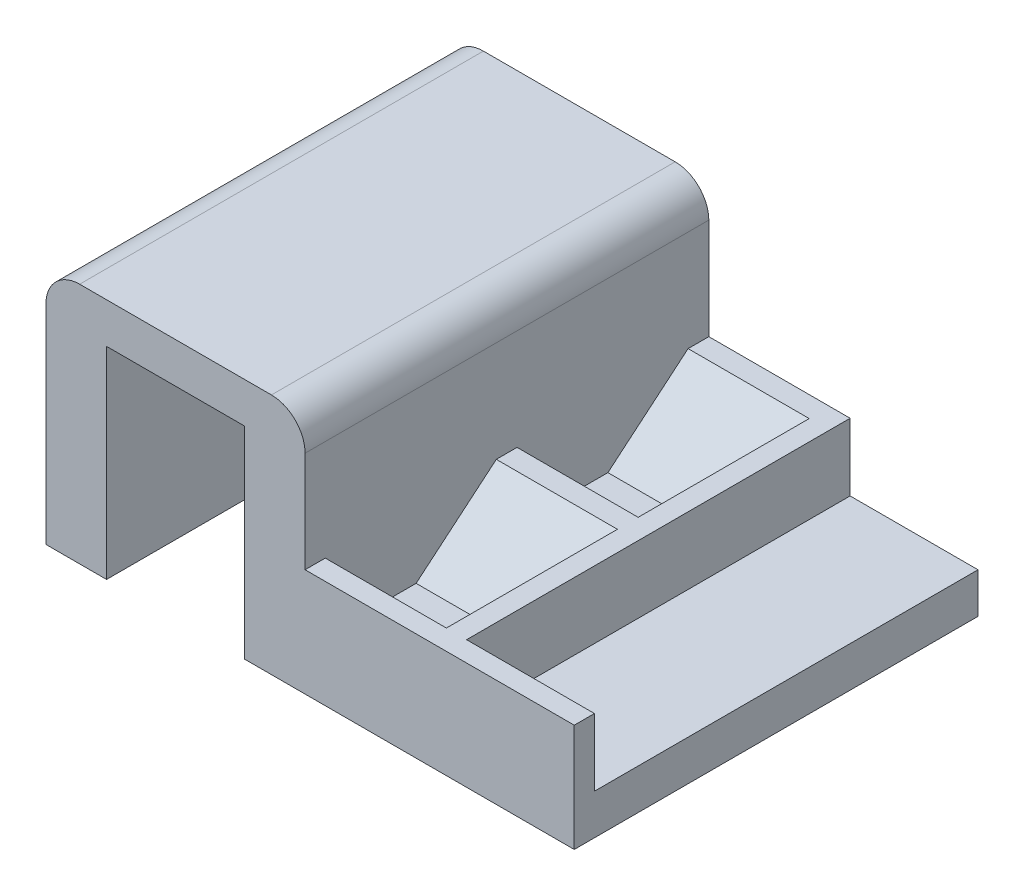
SolidWorks part; units mm, degrees
ref_plane "Front Plane" through (0, 0, 0) normal (0, 0, 1) x (1, 0, 0)
ref_plane "Top Plane" through (0, 0, 0) normal (0, 1, 0) x (1, 0, 0)
ref_plane "Right Plane" through (0, 0, 0) normal (1, 0, 0) x (0, 0, -1)
sketch "Sketch1" plane through (0, 0, 0) normal (0, 0, 1) x (1, 0, 0)
  line L0 (0, 0) -> (0, 30)
  line L1 (0, 30) -> (20.5, 30)
  line L2 (20.5, 30) -> (20.5, 0)
  line L3 (20.5, 0) -> (69.5, 0)
  line L4 (69.5, 0) -> (69.5, 6)
  line L5 (69.5, 6) -> (29.5, 6)
  line L6 (29.5, 6) -> (29.5, 36)
  line L7 (29.5, 36) -> (-9, 36)
  line L8 (-9, 36) -> (-9, 0)
  line L9 (-9, 0) -> (0, 0)
  dimension "D1" = 20.5
  dimension "D2" = 9
  dimension "D3" = 9
  dimension "D4" = 6
  dimension "D5" = 30
  dimension "D6" = 40
  dimension "D7" = 6
extrude "Boss-Extrude1" add sketch "Sketch1" along normal blind 60
sketch "Sketch2" plane through (0, 6, 0) normal (0, 1, 0) x (1, 0, 0)
  line L0 (47.5, 0) -> (47.5, -60)
  line L1 (69.5, 0) -> (29.5, 0) construction
  line L2 (47.5, -60) -> (69.5, -60)
  line L3 (69.5, -60) -> (69.5, 0) construction
  line L4 (69.5, -60) -> (69.5, -57)
  line L5 (69.5, -57) -> (50.5, -57)
  line L6 (50.5, -57) -> (50.5, 0)
  line L7 (50.5, 0) -> (47.5, 0)
  line L8 (47.5, 0) -> (29.5, 0)
  line L9 (29.5, 0) -> (29.5, -3)
  line L10 (29.5, -60) -> (29.5, 0) construction
  line L11 (29.5, -3) -> (47.5, -3)
  line L12 (47.5, -31.5) -> (29.5, -31.5)
  line L13 (29.5, -31.5) -> (29.5, -28.5)
  line L14 (29.5, -28.5) -> (47.5, -28.5)
  line L15 (47.5, -60) -> (29.5, -60)
  line L16 (29.5, -60) -> (29.5, -57)
  line L17 (29.5, -57) -> (47.5, -57)
  point P22 (29.5, -30)
  point P23 (29.5, -30)
  line M10 (69.5, 0) -> (29.5, 0)
  line M11 (29.5, 0) -> (29.5, -60)
  line M12 (29.5, -60) -> (69.5, -60)
  line M13 (69.5, -60) -> (69.5, 0)
  dimension "D1" = 30
  dimension "D2" = 3
extrude "Boss-Extrude2" add sketch "Sketch2" along normal blind 10 contours L11 L0 M11 M10 | L5 L6 L0 M10 M12 M13 | L14 L12 L0 M11 | L17 L0 M11 M12 region at (49, 6, 0.6391) region at (38.5, 6, 1.5) region at (38.5, 6, 30) region at (38.5, 6, 58.5)
chamfer "Chamfer1" distance 12 angle 40 2 edges at (38.5, 6, 31.5) (38.5, 6, 3) first distance on face at (38.5, 6, 44.25) first distance on face at (38.5, 6, 15.75)
fillet "Fillet1" radius 5 2 edges at (29.5, 36, 30) (-9, 36, 30)
